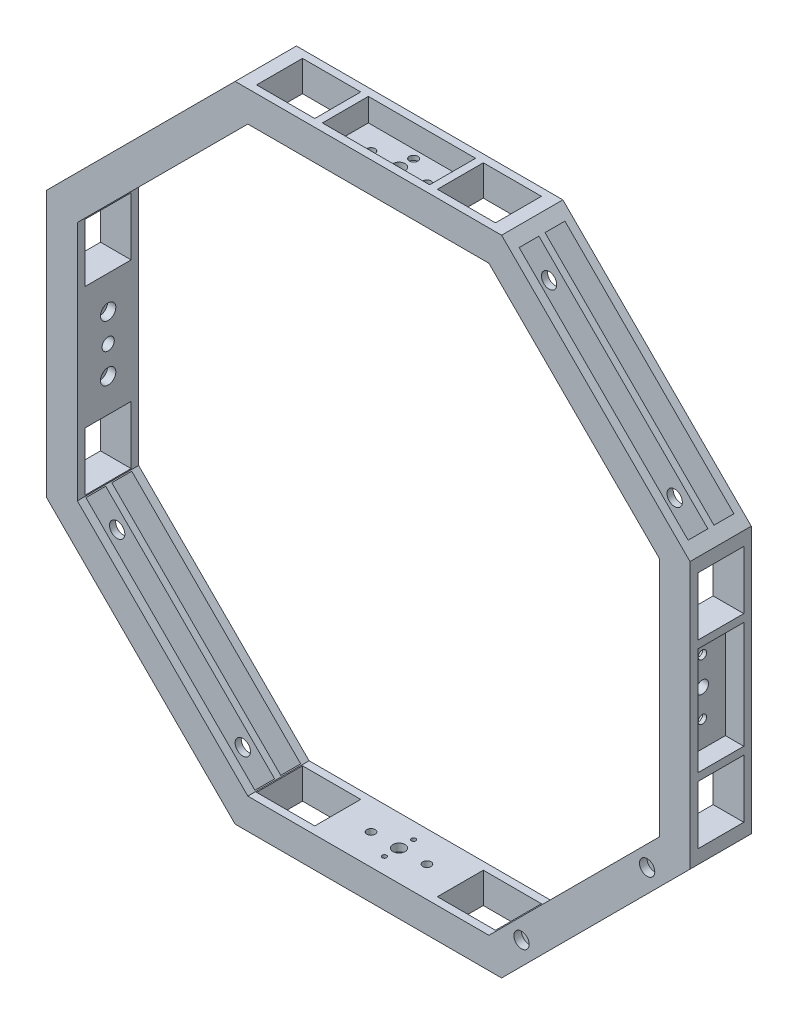
SolidWorks part; units mm, degrees
ref_plane "Plano frontal" through (0, 0, 0) normal (0, 0, 1) x (1, 0, 0)
ref_plane "Plano superior" through (0, 0, 0) normal (0, 1, 0) x (1, 0, 0)
ref_plane "Plano direito" through (0, 0, 0) normal (1, 0, 0) x (0, 0, -1)
sketch "Esboço1" plane through (0, 0, 0) normal (0, 0, 1) x (1, 0, 0)
  line L9 (210, 86.9848) -> (86.9848, 210)
  line L10 (86.9848, 210) -> (-86.9848, 210)
  line L11 (-86.9848, 210) -> (-210, 86.9848)
  line L12 (-210, 86.9848) -> (-210, -86.9848)
  line L13 (-210, -86.9848) -> (-86.9848, -210)
  line L14 (-86.9848, -210) -> (86.9848, -210)
  line L15 (86.9848, -210) -> (210, -86.9848)
  line L16 (210, -86.9848) -> (210, 86.9848)
  line L17 (190, 78.7006) -> (78.7006, 190)
  line L18 (78.7006, 190) -> (-78.7006, 190)
  line L19 (-78.7006, 190) -> (-190, 78.7006)
  line L20 (-190, 78.7006) -> (-190, -78.7006)
  line L21 (-190, -78.7006) -> (-78.7006, -190)
  line L22 (-78.7006, -190) -> (78.7006, -190)
  line L23 (78.7006, -190) -> (190, -78.7006)
  line L24 (190, -78.7006) -> (190, 78.7006)
  circle A0 centre (0, 0) radius 210 construction
  circle A1 centre (0, 0) radius 190 construction
extrude "Ressalto-extrusão1" add sketch "Esboço1" along normal blind 40
sketch "Esboço2" plane through (210, 0, 0) normal (1, 0, 0) x (0, 0, -1)
  line L1 (-4.9012, 78) -> (-4.9012, -78)
  line L23 (-4.9012, 78) -> (-34.9012, 78)
  line L24 (-34.9012, 78) -> (-34.9012, -78)
  line L25 (-4.9012, -78) -> (-34.9012, -78)
  line L26 (-4.9012, 78) -> (-4.9012, -78)
  line L27 (-4.9012, 78) -> (-34.9012, 78)
  line L28 (-34.9012, 78) -> (-34.9012, -78)
  line L29 (-4.9012, -78) -> (-34.9012, -78)
  line L30 (-4.9012, 0) -> (-4.9012, -40)
  line L31 (-34.9012, 0) -> (-34.9012, -40)
  line L32 (-4.9012, -40) -> (-34.9012, -40)
  line L33 (-4.9012, 0) -> (-4.9012, 40)
  line L34 (-34.9012, 0) -> (-34.9012, 40)
  line L35 (-4.9012, 40) -> (-34.9012, 40)
  line L36 (-4.9012, 35) -> (-4.9012, -35)
  line L37 (-4.9012, 35) -> (-34.9012, 35)
  line L38 (-34.9012, 35) -> (-34.9012, -35)
  line L39 (-4.9012, -35) -> (-34.9012, -35)
  circle A0 centre (-19.9012, 0) radius 4
  circle A1 centre (-19.9012, -18.25) radius 2.7
  circle A2 centre (-19.9012, 18.25) radius 2.7
  point P12 (0, 0)
extrude "Corte-extrusão2" cut sketch "Esboço2" against normal up to next and the other way through all contours L1 L32 L24 L25 | A0 | A2 | A1 | L35 L1 L23 L24 region at (210, 59, 19.9012) region at (210, -59, 19.9012) region at (210, 0, 19.9012) region at (210, -18.25, 19.9012) region at (210, 18.25, 19.9012)
sketch "Esboço32" plane through (190, 0, 0) normal (-1, 0, 0) x (0, 0, 1)
  circle A0 centre (19.9012, 18.25) radius 2.7
  circle A1 centre (19.9012, -18.25) radius 2.7
hole_wizard "Rebaixo para parafuso Allen sextavado de M52" positions "Esboço33" profile "Esboço34" counterbore size "M5" standard "ISO" end condition up to next
sketch "Esboço33" plane through (190, 0, 0) normal (-1, 0, 0) x (0, 0, 1)
  point P0 (19.9012, 18.25)
  point P3 (19.9012, -18.25)
sketch "Esboço34" plane through (190, 18.25, 19.9012) normal (0, 1, 0) x (0, 0, 1)
  line L0 (0, 0) -> (0, 20)
  line L1 (0, 20) -> (2.75, 20)
  line L3 (2.75, 20) -> (2.75, 5.4)
  line L4 (2.75, 5.4) -> (5, 5.4)
  line L5 (5, 5.4) -> (5, 0)
  line L7 (5, 0) -> (0, 0)
  line L11 (0, -6.35) -> (0, 107.95) construction
  dimension "Thru Hole Dia." = 5.5
  dimension "Thru Hole Depth" = 20
  dimension "C'Bore Dia." = 10
  dimension "C'Bore Depth" = 5.4
sketch "Esboço15" plane through (-148.4924, 148.4924, 0) normal (-0.7071, 0.7071, 0) x (0, 0, 1)
  line L0 (40, 86.9848) -> (0, 86.9848) construction
  line L1 (5, 86.9848) -> (35, 86.9848)
  line L2 (5, 86.9848) -> (5, -86.9848)
  line L3 (5, -86.9848) -> (35, -86.9848)
  line L4 (35, 86.9848) -> (35, -86.9848)
  line L5 (40, -86.9848) -> (0, -86.9848) construction
  line L9 (20, 86.9848) -> (22, 86.9848)
  line L11 (20, -86.9848) -> (22, -86.9848)
  line L12 (22, 78) -> (22, -78)
  line L14 (20, 86.9848) -> (18, 86.9848)
  line L16 (20, -86.9848) -> (18, -86.9848)
  line L17 (18, 78) -> (18, -78)
  line L19 (5, 86.9848) -> (35, 86.9848)
  line L20 (5, 86.9848) -> (5, 78)
  line L21 (5, 78) -> (35, 78)
  line L22 (35, 86.9848) -> (35, 78)
  line L24 (5, -86.9848) -> (35, -86.9848)
  line L25 (5, -86.9848) -> (5, -78)
  line L26 (5, -78) -> (35, -78)
  line L27 (35, -86.9848) -> (35, -78)
extrude "Corte-extrusão5" cut sketch "Esboço15" against normal up to next contours L12 L26 L4 L21 | L2 L26 L17 L21 region at (-148.4924, 148.4924, 11.5) region at (-148.4924, 148.4924, 28.5)
sketch "Esboço16" plane through (148.4924, 148.4924, 0) normal (0.7071, 0.7071, 0) x (0, 0, -1)
  line L0 (-40, 86.9848) -> (0, 86.9848) construction
  line L2 (-34.9012, -78) -> (-34.9012, 86.9848)
  line L3 (-34.9012, 86.9848) -> (-5, 86.9848)
  line L4 (-5, -86.8738) -> (-5, 86.9848)
  line L8 (-34.9012, -78) -> (-5, -78)
  line L9 (-5, -86.8738) -> (-5, -78)
  line L10 (-5, 86.9848) -> (-34.9012, 86.9848)
  line L11 (-5, 86.9848) -> (-5, 78)
  line L12 (-5, 78) -> (-34.9012, 78)
  line L13 (-34.9012, 86.9848) -> (-34.9012, 78)
  line L14 (-19.9506, 78) -> (-18, 78)
  line L16 (-20, -78) -> (-18, -78)
  line L17 (-18, 78) -> (-18, -78)
  line L18 (-20, -78) -> (-22, -78)
  line L20 (-19.9506, 78) -> (-22, 78)
  line L21 (-22, -78) -> (-22, 78)
  line L22 (-34.9012, -78) -> (-5, -78)
  line L23 (-34.9012, -78) -> (-34.9012, -86.8738)
  line L24 (-34.9012, -86.8738) -> (-5, -86.8738)
  line L25 (-5, -78) -> (-5, -86.8738)
extrude "Corte-extrusão6" cut sketch "Esboço16" against normal through all both and the other way through all contours L8 L21 L12 L2 | L12 L17 L8 L4 region at (148.4924, 148.4924, 28.4506) region at (148.4924, 148.4924, 11.5)
sketch "Esboço18" plane through (0, -210, 0) normal (0, -1, 0) x (1, 0, 0)
  line L1 (-78, 35) -> (78, 35)
  line L2 (-78, 35) -> (-78, 5)
  line L3 (-78, 5) -> (78, 5)
  line L4 (78, 35) -> (78, 5)
  line L5 (-78, 35) -> (78, 35)
  line L6 (-78, 35) -> (-78, 5)
  line L7 (-78, 5) -> (78, 5)
  line L8 (78, 35) -> (78, 5)
  line L9 (0, 35) -> (40.0505, 35)
  line L11 (0, 5) -> (40.0505, 5)
  line L12 (40.0505, 35) -> (40.0505, 5)
  line L13 (0, 35) -> (-40, 35)
  line L15 (0, 5) -> (-40, 5)
  line L16 (-40, 35) -> (-40, 5)
  line L17 (-35, 35) -> (35, 35)
  line L18 (-35, 35) -> (-35, 5)
  line L19 (-35, 5) -> (35, 5)
  line L20 (35, 35) -> (35, 5)
  circle A0 centre (0, 20) radius 4
  circle A1 centre (18.25, 20) radius 2.7
  circle A2 centre (-18.25, 20) radius 2.7
  circle A3 centre (0, 29.53) radius 1.25
  circle A4 centre (0, 10.47) radius 1.25
  line M8 (86.9848, 0) -> (86.9848, 40)
  line M12 (-86.9848, 40) -> (-86.9848, 0)
sketch "Esboço26" plane through (0, 0, 0) normal (0, 0, -1) x (-1, 0, 0)
  circle A0 centre (100, 182) radius 5
  circle A1 centre (182, 100) radius 5
  circle A2 centre (-182, -100) radius 5
  circle A3 centre (-100, -182) radius 5
  circle A4 centre (100, -182) radius 5
  circle A5 centre (182, -100) radius 5
  circle A6 centre (-182, 100) radius 5
  circle A7 centre (-100, 182) radius 5
extrude "Corte-extrusão10" cut sketch "Esboço26" against normal up to next from surface starting at face at (141.4214, 141.4214, 18)
extrude "Corte-extrusão12" cut sketch "Esboço18" against normal through all contours L16 L1 L3 M12 | L1 L12 L3 M8 | A2 | A0 | A1 | A3 | A4 region at (-59, -210, 20) region at (59.0253, -210, 20) region at (0, -210, 20) region at (18.25, -210, 20) region at (-18.25, -210, 20) region at (0, -210, 29.53) region at (0, -210, 10.47)
extrude "Corte-extrusão13" cut sketch "Esboço18<4>" against normal blind 15 contours L20 L5 L13 L18 L15 L7 A2 A1 A0 region at (-17.5, -210, 34.2384)
sketch "Esboço18<4>" plane through (0, -210, 0) normal (0, -1, 0) x (1, 0, 0) same geometry as "Esboço18"
extrude "Corte-extrusão14" cut sketch "Esboço2<5>" against normal blind 12 contours L39 L26 L33 L37 L34 L28 A2 A1 A0 region at (210, 17.5, 5.6628)
sketch "Esboço2<5>" plane through (210, 0, 0) normal (1, 0, 0) x (0, 0, -1) same geometry as "Esboço2"
mirror "Espelhar6" about plane through (0, 0, 0) normal (1, 0, 0) of "Corte-extrusão14", "Rebaixo para parafuso Allen sextavado de M52", "Corte-extrusão2"
hole_wizard "Rebaixo para parafuso Allen sextavado de M2.51" positions "Esboço35" profile "Esboço36" counterbore size "M2.5" standard "ISO" end condition up to next
sketch "Esboço35" plane through (0, -195, 0) normal (0, -1, 0) x (-1, 0, 0)
  point P0 (0, -10.47)
  point P3 (0, -29.53)
sketch "Esboço36" plane through (0, -195, 10.47) normal (1, 0, 0) x (0, 0, -1)
  line L0 (0, 0) -> (0, 405)
  line L1 (0, 405) -> (1.45, 405)
  line L3 (1.45, 405) -> (1.45, 2.9)
  line L4 (1.45, 2.9) -> (2.75, 2.9)
  line L5 (2.75, 2.9) -> (2.75, 0)
  line L7 (2.75, 0) -> (0, 0)
  line L11 (0, -6.35) -> (0, 107.95) construction
  dimension "Thru Hole Dia." = 2.9
  dimension "Thru Hole Depth" = 405
  dimension "C'Bore Dia." = 5.5
  dimension "C'Bore Depth" = 2.9
ref_plane "Plano1" through (0, 0, 0) normal (-0.7071, 0.7071, 0) x (0.7071, 0.7071, 0)
mirror "Espelhar8" about plane through (0, 0, 0) normal (-0.7071, 0.7071, 0) of "Corte-extrusão5"
mirror "Espelhar9" about plane through (0, 0, 0) normal (0, 1, 0) of "Rebaixo para parafuso Allen sextavado de M2.51", "Corte-extrusão12", "Corte-extrusão13"
